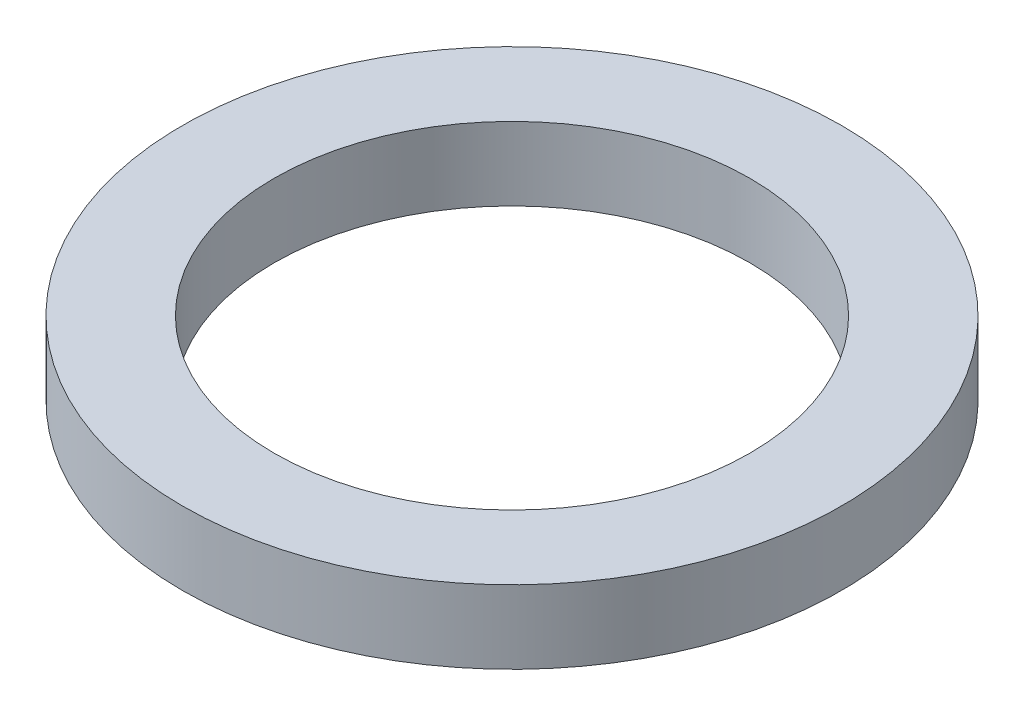
SolidWorks part; units mm, degrees
ref_plane "Front Plane" through (0, 0, 0) normal (0, 0, 1) x (1, 0, 0)
ref_plane "Top Plane" through (0, 0, 0) normal (0, 1, 0) x (1, 0, 0)
ref_plane "Right Plane" through (0, 0, 0) normal (1, 0, 0) x (0, 0, -1)
sketch "Sketch1" plane through (0, 0, 0) normal (0, 1, 0) x (1, 0, 0)
  circle A0 centre (0, 0) radius 45
  dimension "FLANGE_OD" = 90
extrude "Boss-Extrude1" add sketch "Sketch1" along normal blind 10
sketch "Sketch2" plane through (0, 0, 0) normal (0, 1, 0) x (1, 0, 0)
  circle A0 centre (0, 0) radius 32.5
  dimension "BORE_D" = 65
extrude "Cut-Extrude1" cut sketch "Sketch2" along normal through all
sketch "Sketch3" plane through (0, 10, 0) normal (0, 1, 0) x (1, 0, 0)
  circle A0 centre (0, 0) radius 20.1368 construction
  circle A1 centre (-20.1368, 0) radius 1.8439
  dimension "BOLT_D" = 3.6879
  dimension "BOLT_PCD" = 40.2736
extrude "Cut-Extrude2" cut sketch "Sketch3" against normal blind 8.4504 rebuild error yes
pattern_circular "CirPattern1" count 4 over 360 rebuild error yes
